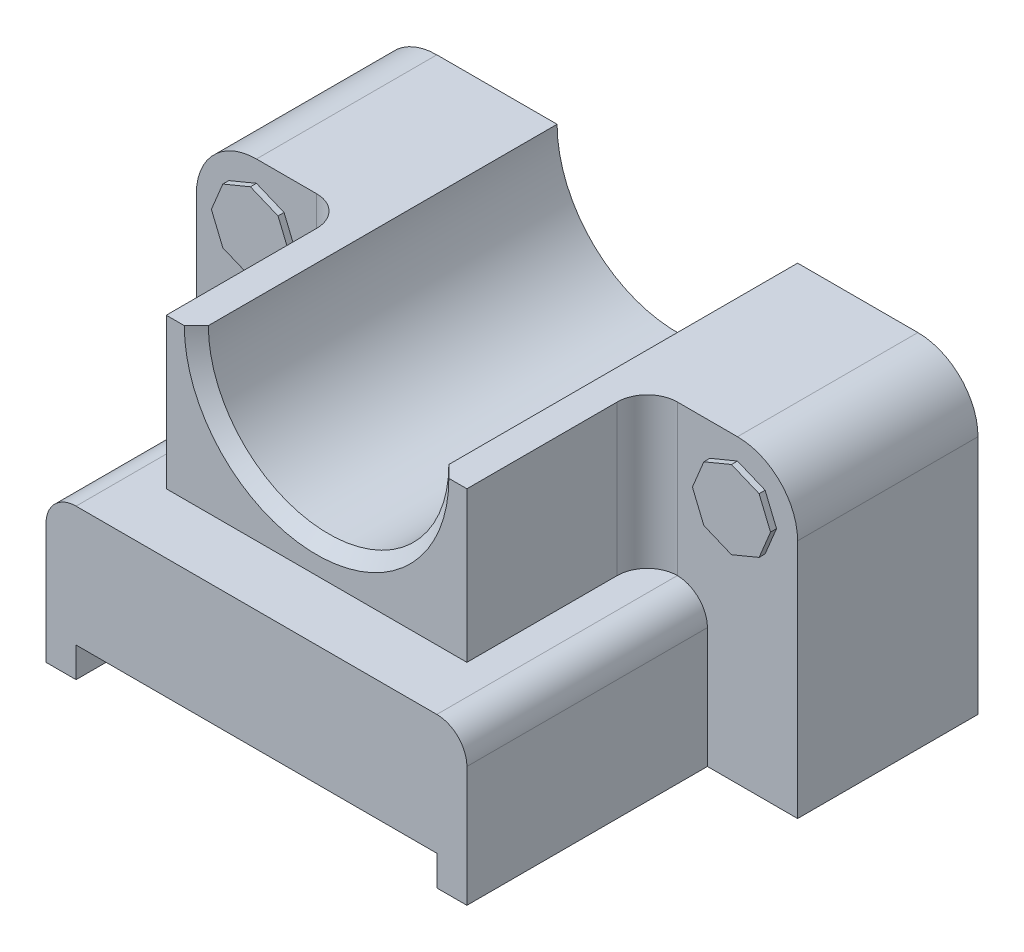
SolidWorks part; units mm, degrees
ref_plane "Alzado" through (0, 0, 0) normal (0, 0, 1) x (1, 0, 0)
ref_plane "Planta" through (0, 0, 0) normal (0, 1, 0) x (1, 0, 0)
ref_plane "Vista lateral" through (0, 0, 0) normal (1, 0, 0) x (0, 0, -1)
sketch "Croquis1" plane through (0, 0, 0) normal (0, 0, 1) x (1, 0, 0)
  line L1 (-50, -25) -> (50, -25)
  line L2 (-50, -25) -> (-50, 25)
  line L3 (-50, 25) -> (50, 25)
  line L4 (50, -25) -> (50, 25)
  line L5 (-50, -25) -> (50, 25) construction
  line L6 (-50, 25) -> (50, -25) construction
  point P0 (0, 0)
  dimension "D1" = 100
  dimension "D2" = 50
extrude "Saliente-Extruir1" add sketch "Croquis1" along normal blind 30
sketch "Croquis2" plane through (0, 0, 30) normal (0, 0, 1) x (1, 0, 0)
  line L0 (-50, -25) -> (50, -25) construction
  line L1 (-35, -25) -> (35, -25)
  line L2 (-35, -25) -> (-35, 0)
  line L3 (-35, 0) -> (35, 0)
  line L4 (35, -25) -> (35, 0)
  line L5 (50, -25) -> (50, 25) construction
  dimension "D1" = 70
  dimension "D2" = 25
  dimension "D3" = 15
extrude "Saliente-Extruir2" add sketch "Croquis2" along normal blind 40
sketch "Croquis3" plane through (0, 0, 30) normal (0, 0, 1) x (1, 0, 0)
  line L0 (35, 0) -> (-35, 0) construction
  line L1 (-25, 0) -> (25, 0)
  line L2 (-25, 0) -> (-25, 25)
  line L3 (-25, 25) -> (25, 25)
  line L4 (25, 0) -> (25, 25)
  line L5 (50, 25) -> (-50, 25) construction
  line L6 (50, -25) -> (50, 25) construction
  point P10 (0, 0)
  dimension "D2" = 50
  dimension "D3" = 25
extrude "Saliente-Extruir3" add sketch "Croquis3" along normal blind 30
sketch "Croquis4" plane through (0, 0, 60) normal (0, 0, 1) x (1, 0, 0)
  line L0 (25, 25) -> (-25, 25) construction
  circle A0 centre (0, 25) radius 20
  dimension "D1" = 40
extrude "Cortar-Extruir1" cut sketch "Croquis4" against normal through all
chamfer "Chaflán1" distance 2 angle 45 1 edges at (0, 5, 60)
sketch "Croquis5" plane through (0, 0, 70) normal (0, 0, 1) x (1, 0, 0)
  line L0 (-35, -25) -> (35, -25) construction
  line L1 (-30, -25) -> (30, -25)
  line L2 (-30, -25) -> (-30, -20)
  line L3 (-30, -20) -> (30, -20)
  line L4 (30, -25) -> (30, -20)
  line L5 (-35, 0) -> (-35, -25) construction
  point P6 (-30, -22.5)
  dimension "D1" = 60
  dimension "D2" = 5
  dimension "D3" = 5
extrude "Cortar-Extruir2" cut sketch "Croquis5" against normal through all
fillet "Redondeo1" radius 10 2 edges at (-50, 25, 15) (50, 25, 15)
fillet "Redondeo2" radius 5 4 edges at (-35, 0, 50) (35, 0, 50) (-25, 12.5, 30) (25, 12.5, 30)
sketch "Croquis6" plane through (0, 0, 30) normal (0, 0, 1) x (1, 0, 0)
  circle A0 centre (-40, 15) radius 5
  circle A1 centre (40, 15) radius 5
  dimension "D1" = 10
extrude "Cortar-Extruir3" cut sketch "Croquis6" against normal through all
sketch "Croquis9" plane through (0, 0, 30) normal (0, 0, 1) x (1, 0, 0)
  line L1 (-40, 21.4944) -> (-44.5922, 19.5922)
  line L2 (-44.5922, 19.5922) -> (-46.4944, 15)
  line L3 (-46.4944, 15) -> (-44.5922, 10.4078)
  line L4 (-44.5922, 10.4078) -> (-40, 8.5056)
  line L5 (-40, 8.5056) -> (-35.4078, 10.4078)
  line L6 (-35.4078, 10.4078) -> (-33.5056, 15)
  line L7 (-33.5056, 15) -> (-35.4078, 19.5922)
  line L8 (-35.4078, 19.5922) -> (-40, 21.4944)
  line L9 (40, 21.4944) -> (35.4078, 19.5922)
  line L10 (35.4078, 19.5922) -> (33.5056, 15)
  line L11 (33.5056, 15) -> (35.4078, 10.4078)
  line L12 (35.4078, 10.4078) -> (40, 8.5056)
  line L13 (40, 8.5056) -> (44.5922, 10.4078)
  line L14 (44.5922, 10.4078) -> (46.4944, 15)
  line L15 (46.4944, 15) -> (44.5922, 19.5922)
  line L16 (44.5922, 19.5922) -> (40, 21.4944)
  circle A0 centre (-40, 15) radius 6 construction
  circle A1 centre (40, 15) radius 6 construction
extrude "Saliente-Extruir4" add sketch "Croquis9" along normal blind 1
sketch "Croquis10" plane through (0, 0, 70) normal (0, 0, 1) x (1, 0, 0)
  line L0 (-28.5912, -14.347) -> (28.4883, -14.347) construction
  text T0 "SOLIDWORKS 2026" font "Century Gothic" height 4.5
